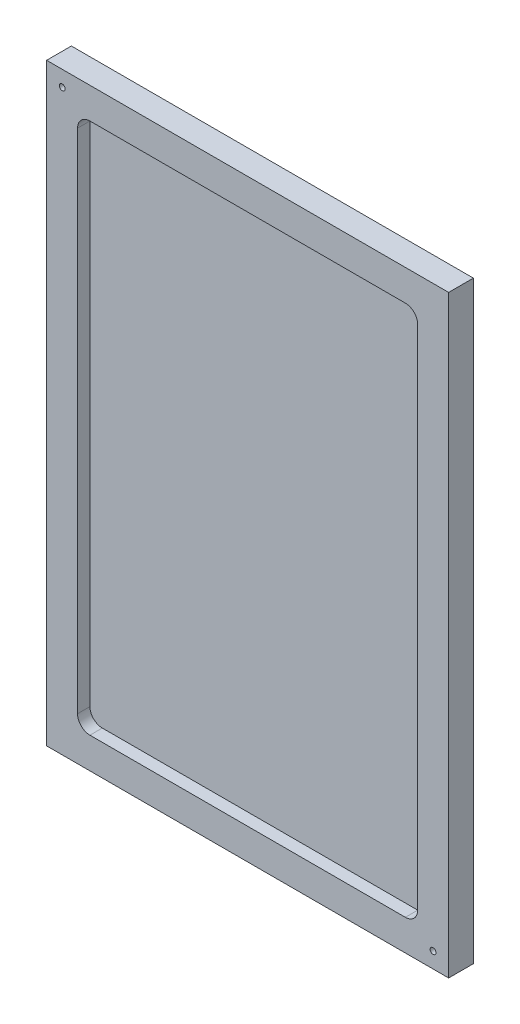
SolidWorks part; units mm, degrees
ref_plane "Front Plane" through (0, 0, 0) normal (0, 0, 1) x (1, 0, 0)
ref_plane "Top Plane" through (0, 0, 0) normal (0, 1, 0) x (1, 0, 0)
ref_plane "Right Plane" through (0, 0, 0) normal (1, 0, 0) x (0, 0, -1)
sketch "Sketch1" plane through (0, 0, 0) normal (0, 0, 1) x (1, 0, 0)
  line L1 (103.1875, -152.4) -> (-103.1875, -152.4)
  line L2 (103.1875, -152.4) -> (103.1875, 152.4)
  line L3 (103.1875, 152.4) -> (-103.1875, 152.4)
  line L4 (-103.1875, -152.4) -> (-103.1875, 152.4)
  line L5 (103.1875, -152.4) -> (-103.1875, 152.4) construction
  line L6 (103.1875, 152.4) -> (-103.1875, -152.4) construction
  point P0 (0, 0)
  dimension "D1" = 304.8
  dimension "D2" = 206.375
extrude "Boss-Extrude1" add sketch "Sketch1" along normal blind 12.7
sketch "Sketch2" plane through (0, 0, 12.7) normal (0, 0, 1) x (1, 0, 0)
  line L0 (-103.1875, 152.4) -> (-103.1875, -152.4) construction
  line L1 (80.9625, -136.525) -> (-80.9625, -136.525)
  line L2 (87.3125, -130.175) -> (87.3125, 130.175)
  line L3 (80.9625, 136.525) -> (-80.9625, 136.525)
  line L4 (-87.3125, -130.175) -> (-87.3125, 130.175)
  line L5 (87.3125, -136.525) -> (-87.3125, 136.525) construction
  line L6 (87.3125, 136.525) -> (-87.3125, -136.525) construction
  line L7 (103.1875, 152.4) -> (-103.1875, 152.4) construction
  arc A0 (-80.9625, -136.525) -> (-87.3125, -130.175) centre (-80.9625, -130.175) cw
  arc A1 (80.9625, -136.525) -> (87.3125, -130.175) centre (80.9625, -130.175) ccw
  arc A2 (87.3125, 130.175) -> (80.9625, 136.525) centre (80.9625, 130.175) ccw
  arc A3 (-80.9625, 136.525) -> (-87.3125, 130.175) centre (-80.9625, 130.175) ccw
  point P0 (0, 0)
  dimension "D3" = 6.35
  dimension "D1" = 15.875
  dimension "D2" = 15.875
extrude "Cut-Extrude1" cut sketch "Sketch2" against normal blind 6.35
sketch "Sketch3" plane through (0, 0, 12.7) normal (0, 0, 1) x (1, 0, 0)
  line L0 (95.6521, -142.2937) -> (97.3079, -144.7953) construction
  line L1 (94.7229, -146.5063) -> (93.0671, -144.0047) construction
  line L2 (95.6521, -142.2937) -> (97.3079, -144.7953) construction
  line L3 (94.7229, -146.5063) -> (93.0671, -144.0047) construction
  circle A0 centre (-95.1875, 144.4) radius 1.55 construction
  arc A1 (95.6521, -142.2937) -> (93.0671, -144.0047) centre (94.3596, -143.1492) ccw construction
  arc A2 (94.7229, -146.5063) -> (97.3079, -144.7953) centre (96.0154, -145.6508) ccw construction
  circle A3 centre (-95.1875, 144.4) radius 1.55 construction
  arc A4 (95.6521, -142.2937) -> (93.0671, -144.0047) centre (94.3596, -143.1492) ccw construction
  arc A5 (94.7229, -146.5063) -> (97.3079, -144.7953) centre (96.0154, -145.6508) ccw construction
hole_wizard "Ø3.0 (3) Diameter Hole1" positions "3DSketch1" profile "Sketch4" hole size "Ø3.0" standard "ANSI Metric"
sketch3d "3DSketch1"
  line L0 (-103.1875, -152.4, 12.7) -> (103.1875, -152.4, 12.7) construction
  line L1 (103.1875, -152.4, 12.7) -> (103.1875, 152.4, 12.7) construction
  line L2 (-103.1875, 152.4, 12.7) -> (-103.1875, -152.4, 12.7) construction
  line L3 (103.1875, 152.4, 12.7) -> (-103.1875, 152.4, 12.7) construction
  point P0 (-95.1875, 144.4, 12.7)
  point P2 (95.1875, -144.4, 12.7)
  point P5 (95.3414, -144.634, 12.7)
  dimension "D1" = 8
  dimension "D2" = 8
  dimension "D3" = 8
  dimension "D4" = 8
sketch "Sketch4" plane through (-95.1875, 144.4, 12.7) normal (1, 0, 0) x (0, -1, 0)
  line L0 (0, 0) -> (0, 5.9013)
  line L1 (0, 5.9013) -> (1.5, 5)
  line L2 (1.5, 5) -> (1.5, 0)
  line L5 (1.5, 0) -> (0, 0)
  line L10 (0, 5.9013) -> (-1.5, 5) construction
  line L11 (0, -6.35) -> (0, 107.95) construction
  dimension "Hole Dia." = 3
  dimension "Hole Depth" = 5
  dimension "Drill Angle" = 118
